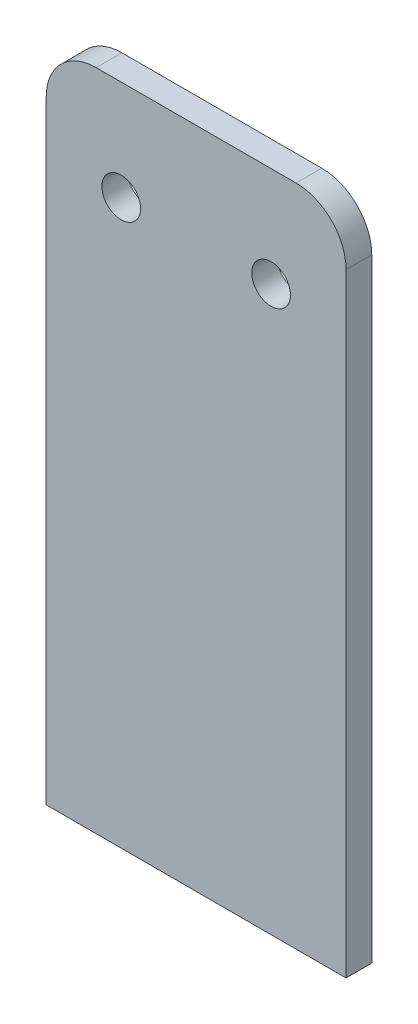
SolidWorks part; units mm, degrees
ref_plane "Front Plane" through (0, 0, 0) normal (0, 0, 1) x (1, 0, 0)
ref_plane "Top Plane" through (0, 0, 0) normal (0, 1, 0) x (1, 0, 0)
ref_plane "Right Plane" through (0, 0, 0) normal (1, 0, 0) x (0, 0, -1)
sketch "Sketch1" plane through (0, 0, 0) normal (0, 0, 1) x (1, 0, 0)
  line L1 (-19.05, -42.1545) -> (19.05, -42.1545)
  line L2 (-19.05, -42.1545) -> (-19.05, 42.1545)
  line L3 (-19.05, 42.1545) -> (19.05, 42.1545)
  line L4 (19.05, -42.1545) -> (19.05, 42.1545)
  line L5 (-19.05, -42.1545) -> (19.05, 42.1545) construction
  line L6 (-19.05, 42.1545) -> (19.05, -42.1545) construction
  point P0 (0, 0)
  dimension "D1" = 84.3089
  dimension "D2" = 38.1
base flange "Base-Flange1" sketch "Sketch1" thickness 3.2639 reverse thickness direction no parameters "D1"=2.286
hole_wizard "#10 (0.1935) Diameter Hole1" positions "Sketch8" profile "Sketch7" hole size "#10" standard "ANSI Inch" end condition through all
sketch "Sketch8" plane through (0, 0, 0) normal (0, 0, 1) x (1, 0, 0)
  line L0 (0, 42.1545) -> (0, -42.1545) construction
  line L1 (19.05, 42.1545) -> (-19.05, 42.1545) construction
  line L2 (-19.05, -42.1545) -> (19.05, -42.1545) construction
  line L5 (-19.05, 29.4545) -> (19.05, 29.4545) construction
  line L6 (-19.05, 42.1545) -> (-19.05, -42.1545) construction
  line L7 (19.05, -42.1545) -> (19.05, 42.1545) construction
  point P0 (-9.525, 29.4545)
  point P2 (9.525, 29.4545)
  dimension "D1" = 12.7
  dimension "D2" = 9.525
  dimension "D3" = 19.05
sketch "Sketch7" plane through (-9.525, 29.4545, 0) normal (1, 0, 0) x (0, -1, 0)
  line L0 (0, 0) -> (0, 3.2639)
  line L1 (0, 3.2639) -> (2.4574, 3.2639)
  line L2 (2.4574, 3.2639) -> (2.4574, 0)
  line L5 (2.4574, 0) -> (0, 0)
  line L11 (0, -6.35) -> (0, 107.95) construction
  dimension "Thru Hole Dia." = 4.9149
  dimension "Thru Hole Depth" = 3.2639
fillet "Fillet1" radius 6.35 2 edges at (-19.05, 42.1545, -1.632) (19.05, 42.1545, -1.632)
sketch "Bend-Lines1" [suppressed] plane through (0, 0, 0) normal (0, 1, 0) x (1, 0, 0)
sketch "Bounding-Box1" [suppressed] plane through (0, 0, 0) normal (0, 1, 0) x (1, 0, 0)
sheet metal parameters "Sheet-Metal1" thickness 3.2639 parameters "D1"=2
flat pattern "Flat-Pattern1" [suppressed]
sketch "Bend-Lines2" plane through (0, 0, 0) normal (0, 1, 0) x (1, 0, 0)
sketch3d "Bounding-Box2" [suppressed]
  line L0 (-25.4, 36.5125, 0) -> (-25.4, -36.5125, 0) construction
  line L1 (25.4, 36.5125, 0) -> (25.4, -36.5125, 0) construction
  line L2 (-25.4, 36.5125, 0) -> (25.4, 36.5125, 0) construction
  line L3 (-25.4, -36.5125, 0) -> (25.4, -36.5125, 0) construction
sheet metal parameters "Sheet-Metal2" thickness 3.2639 parameters "D1"=2
flat pattern "Flat-Pattern1"
sketch "Bend-Lines2" plane through (0, 0, 0) normal (0, 1, 0) x (1, 0, 0)
sketch3d "Bounding-Box2" [suppressed]
  line L0 (19.05, -42.1545, 0) -> (19.05, 42.1545, 0) construction
  line L1 (-19.05, -42.1545, 0) -> (-19.05, 42.1545, 0) construction
  line L2 (19.05, -42.1545, 0) -> (-19.05, -42.1545, 0) construction
  line L3 (19.05, 42.1545, 0) -> (-19.05, 42.1545, 0) construction
